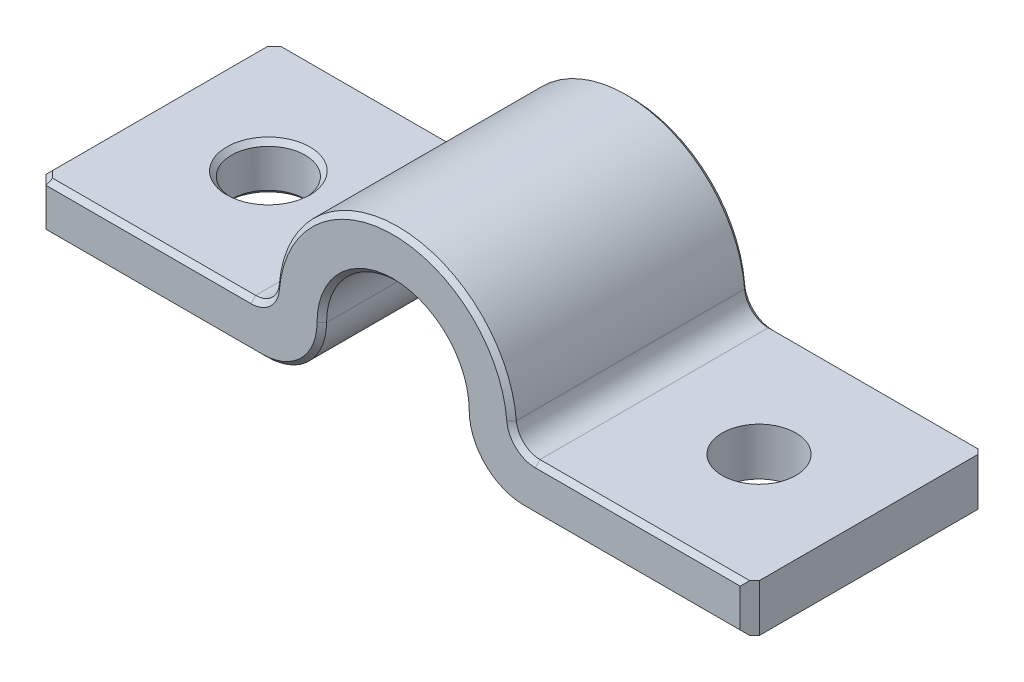
SolidWorks part; units mm, degrees
ref_plane "前视基准面" through (0, 0, 0) normal (0, 0, 1) x (1, 0, 0)
ref_plane "上视基准面" through (0, 0, 0) normal (0, 1, 0) x (1, 0, 0)
ref_plane "右视基准面" through (0, 0, 0) normal (1, 0, 0) x (0, 0, -1)
other "Configuration Table"
sketch "草图4" plane through (0, 0, 0) normal (0, 0, 1) x (1, 0, 0)
  line L4 (-5, 0) -> (-5, -0.5)
  line L5 (-5, -2.5) -> (-3, -2.5)
  line L6 (-3, 0) -> (-3, -2.5)
  line L8 (5, 0) -> (5, -0.5)
  line L9 (5, -2.5) -> (3, -2.5)
  line L10 (3, 0) -> (3, -2.5)
  line L11 (-5, -2.5) -> (-15, -2.5)
  line L13 (-5, -0.5) -> (-15, -0.5)
  line L14 (-15, -2.5) -> (-15, -0.5)
  line L15 (5, -2.5) -> (15, -2.5)
  line L17 (5, -0.5) -> (15, -0.5)
  line L18 (15, -2.5) -> (15, -0.5)
  arc A0 (3, 0) -> (-3, 0) centre (0, 0) ccw
  arc A1 (5, 0) -> (-5, 0) centre (0, 0) ccw
  dimension "D1" = 6
  dimension "D2" = 10
  dimension "D8" = 0
  dimension "D3" = 2.5
  dimension "D4" = 2.5
  dimension "D5" = 2
  dimension "D6" = 2
  dimension "D7" = 10
  dimension "D9" = 10
extrude "凸台-拉伸3" add sketch "草图4" along normal blind 10
fillet "圆角2" radius 1 2 edges at (5, -0.5, 5) (-5, -0.5, 5)
fillet "圆角3" radius 2.5 2 edges at (-3, -2.5, 5) (3, -2.5, 5)
chamfer "倒角1" distance 0.4 angle 45 4 edges at (15, -1.5, 10) (15, -1.5, 0) (-15, -1.5, 10) (-15, -1.5, 0)
sketch "草图5" plane through (0, -0.5, 0) normal (0, 1, 0) x (1, 0, 0)
  circle A0 centre (-10.2481, -5) radius 1.55
  circle A1 centre (10.3896, -5) radius 1.55
  dimension "D1" = 3.1
  dimension "D2" = 3.1
extrude "切除-拉伸2" cut sketch "草图5" against normal blind 12
chamfer "倒角2" distance 0.2 angle 45 28 edges at (10.05, -2.5, 0) (10.05, -2.5, 10) (3.7322, -1.7678, 0) (3.7322, -1.7678, 10) (0, 3, 0) (0, 3, 10) (-3.7322, -1.7678, 0) (-3.7322, -1.7678, 10) (-10.05, -2.5, 0) (-14.8, -2.5, 0.2) (-15, -2.5, 5) (-14.8, -2.5, 9.8) (-10.05, -2.5, 10) (10.2896, -0.5, 0) (10.2896, -0.5, 10) (5.3021, -0.236, 0) (5.3021, -0.236, 10) (0, 5, 0) (0, 5, 10) (-5.3021, -0.236, 0) (-5.3021, -0.236, 10) (-10.2896, -0.5, 0) (-14.8, -0.5, 0.2) (-10.2896, -0.5, 10) (-14.8, -0.5, 9.8) (-15, -0.5, 5) (-10.2481, -2.5, 6.55) (-11.7981, -0.5, 5)
